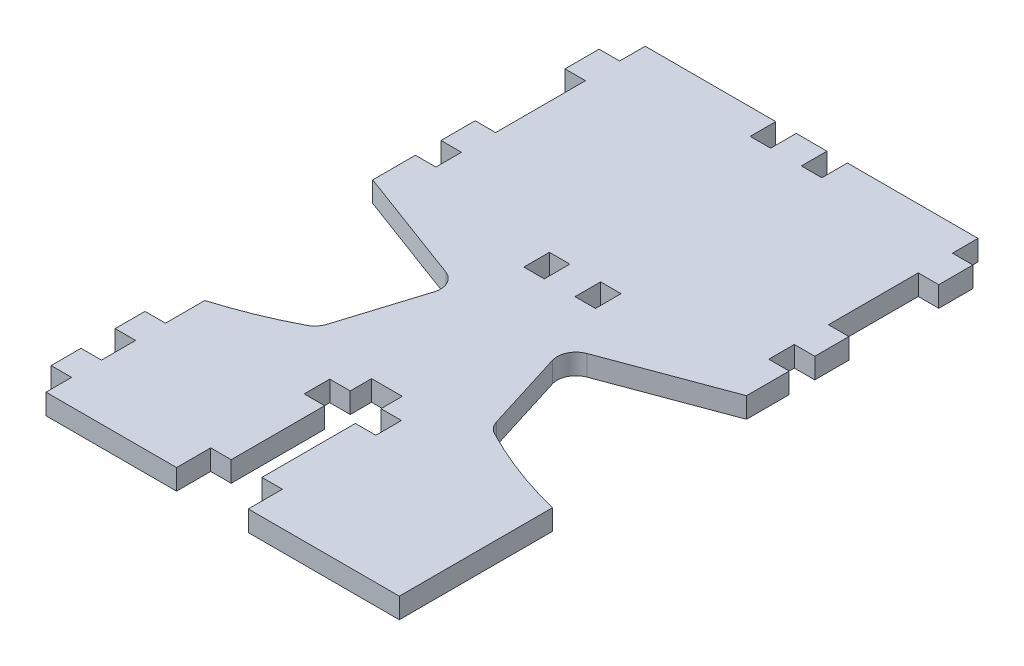
SolidWorks part; units mm, degrees
ref_plane "Front" through (0, 0, 0) normal (0, 0, 1) x (1, 0, 0)
ref_plane "Top" through (0, 0, 0) normal (0, 1, 0) x (1, 0, 0)
ref_plane "Right" through (0, 0, 0) normal (1, 0, 0) x (0, 0, -1)
ref_axis "side-side" through (80.9, 0, 0) along (-1, 0, 0)
ref_axis "up-down" through (0, 50, 0) along (0, -1, 0)
ref_axis "front-back" through (0, 0, -80.9) along (0, 0, 1)
sketch "Sketch1" plane through (0, 0, 0) normal (0, 1, 0) x (1, 0, 0)
  line L0 (0, 45.72) -> (0, 82.7528) construction
  line L1 (-49.53, 45.72) -> (-10.668, 45.72)
  line L2 (-55.626, 38.1) -> (-55.626, 27.94)
  line L3 (-49.53, -132.6173) -> (-10.668, -132.6173)
  line L4 (55.626, 38.1) -> (55.626, 27.94)
  line L6 (10.668, -132.6173) -> (55.626, -132.6173)
  line L7 (4.572, -122.4573) -> (10.668, -122.4573)
  line L8 (-17.632, -49.0369) -> (-25.1877, -73.287)
  line L9 (-21.0198, -42.1368) -> (-55.626, -29.2719)
  line L10 (-55.626, -97.0573) -> (-55.626, -105.9473)
  line L11 (55.626, -29.2719) -> (21.0198, -42.1368)
  line L12 (17.632, -49.0369) -> (25.1877, -73.287)
  line L13 (55.626, -87.0224) -> (55.626, -132.6173)
  line L14 (55.626, -16.5719) -> (55.626, -29.2719)
  line L15 (-49.53, 38.1) -> (-55.626, 38.1)
  line L16 (-49.53, 38.1) -> (-49.53, 45.72)
  line L17 (-55.626, -16.5719) -> (-55.626, -29.2719)
  line L18 (-55.626, 1.2081) -> (-55.626, -8.9519)
  line L19 (-49.53, -8.9519) -> (-55.626, -8.9519)
  line L20 (-49.53, -8.9519) -> (-49.53, -16.5719)
  line L21 (-49.53, -16.5719) -> (-55.626, -16.5719)
  line L22 (-55.626, 27.94) -> (-49.53, 27.94)
  line L23 (-57.4537, -89.4373) -> (-47.6065, -89.4373) construction
  line L25 (55.626, 38.1) -> (49.53, 38.1)
  line L26 (49.53, 45.72) -> (49.53, 38.1)
  line L27 (55.626, -16.5719) -> (49.53, -16.5719)
  line L29 (55.626, -8.9519) -> (49.53, -8.9519)
  line L30 (49.53, -16.5719) -> (49.53, -8.9519)
  line L31 (-55.626, -124.9973) -> (-49.53, -124.9973)
  line L32 (-49.53, -132.6173) -> (-49.53, -124.9973)
  line L33 (-4.572, -94.6424) -> (-4.572, -122.4573)
  line L34 (4.572, -94.6424) -> (4.572, -122.4573)
  line L36 (4.572, -94.6424) -> (10.668, -94.6424)
  line L37 (-10.668, -87.0224) -> (-4.572, -87.0224)
  line L38 (-10.668, -87.0224) -> (-10.668, -94.6424)
  line L39 (-55.626, -97.0573) -> (-49.53, -97.0573)
  line L40 (-49.53, -85.3598) -> (-49.53, -97.0573)
  line L41 (-10.668, -94.6424) -> (-4.572, -94.6424)
  line L42 (10.668, -87.0224) -> (10.668, -94.6424)
  line L43 (10.668, 45.72) -> (49.53, 45.72)
  line L44 (-10.668, -132.6173) -> (-10.668, -122.4573)
  line L45 (-10.668, -122.4573) -> (-4.572, -122.4573)
  line L46 (10.668, -132.6173) -> (10.668, -122.4573)
  line L47 (-4.572, 45.72) -> (4.572, 45.72)
  line L48 (-10.668, 45.72) -> (-10.668, 38.1)
  line L49 (-10.668, 38.1) -> (-4.572, 38.1)
  line L50 (-4.572, 45.72) -> (-4.572, 38.1)
  line L52 (4.572, 45.72) -> (4.572, 38.1)
  line L53 (4.572, 38.1) -> (10.668, 38.1)
  line L54 (10.668, 45.72) -> (10.668, 38.1)
  line L55 (10.668, -21.6519) -> (4.572, -21.6519)
  line L56 (10.668, -21.6519) -> (10.668, -29.2719)
  line L57 (10.668, -29.2719) -> (4.572, -29.2719)
  line L58 (4.572, -21.6519) -> (4.572, -29.2719)
  line L59 (-10.668, -21.6519) -> (-4.572, -21.6519)
  line L60 (-10.668, -21.6519) -> (-10.668, -29.2719)
  line L61 (-10.668, -29.2719) -> (-4.572, -29.2719)
  line L62 (-4.572, -21.6519) -> (-4.572, -29.2719)
  line L64 (-4.572, -87.0224) -> (-4.572, -80.6724)
  line L65 (-4.572, -80.6724) -> (4.572, -80.6724)
  line L66 (4.572, -87.0224) -> (4.572, -80.6724)
  line L68 (4.572, -87.0224) -> (10.668, -87.0224)
  line L70 (55.626, 1.2081) -> (55.626, -8.9519)
  line L71 (-55.626, 1.2081) -> (-49.53, 1.2081)
  line L72 (-49.53, 27.94) -> (-49.53, 1.2081)
  line L73 (55.626, 27.94) -> (49.53, 27.94)
  line L74 (-55.626, -116.1073) -> (-55.626, -124.9973)
  line L75 (55.626, 1.2081) -> (49.53, 1.2081)
  line L76 (49.53, 27.94) -> (49.53, 1.2081)
  line L77 (-55.626, -105.9473) -> (-49.53, -105.9473)
  line L79 (-55.626, -116.1073) -> (-49.53, -116.1073)
  line L80 (-49.53, -105.9473) -> (-49.53, -116.1073)
  arc A1 (-17.632, -49.0369) -> (-21.0198, -42.1368) centre (-22.967, -47.3746) ccw
  arc A2 (-27.9391, -76.5796) -> (-25.1877, -73.287) centre (-30.5228, -71.6248) ccw
  arc A3 (-27.9391, -76.5796) -> (-49.53, -85.3598) centre (-85.09, 33.02) cw
  arc A4 (21.0198, -42.1368) -> (17.632, -49.0369) centre (22.967, -47.3746) ccw
  arc A5 (25.1877, -73.287) -> (27.9391, -76.5796) centre (30.5228, -71.6248) ccw
  arc A6 (27.9391, -76.5796) -> (55.626, -87.0224) centre (85.09, 33.02) ccw
  dimension "D2" = 10.16
  dimension "D1" = 10.16
  dimension "D3" = 8.89
  dimension "D4" = 8.89
extrude "Boss-Extrude1" add sketch "Sketch1" along normal mid plane 6.096
